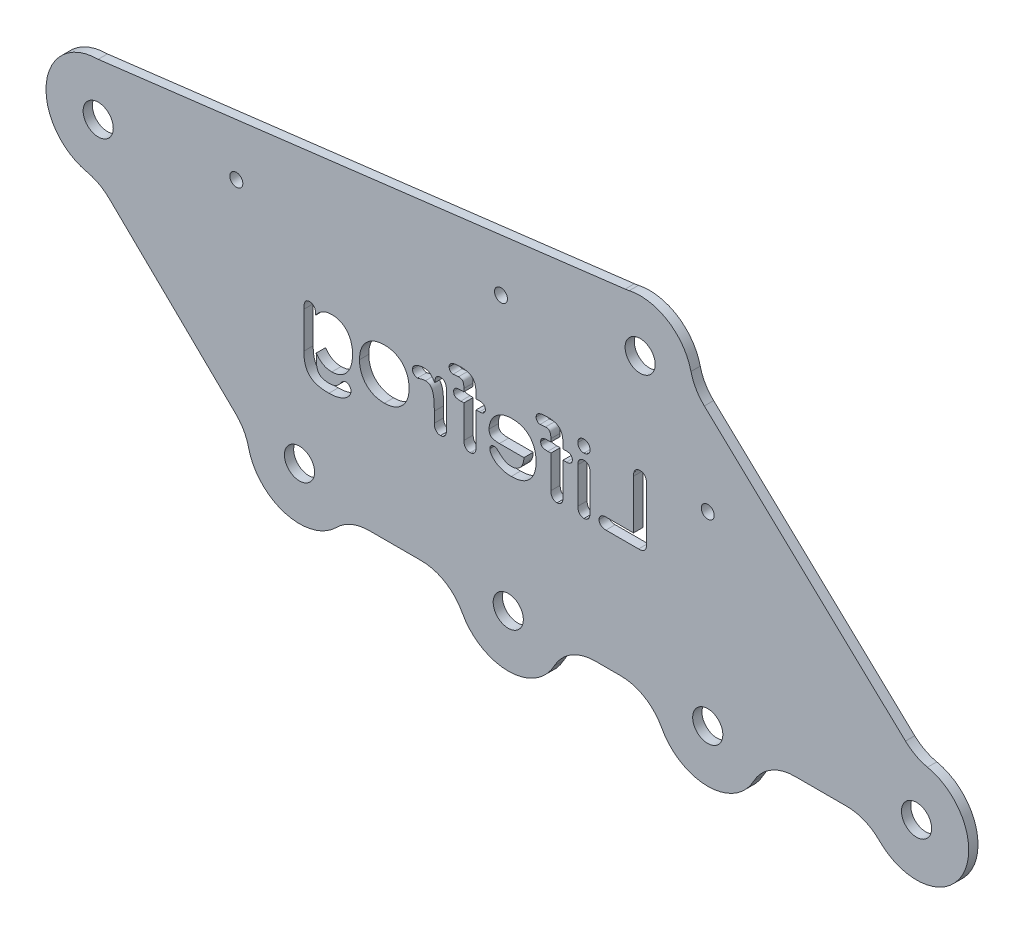
SolidWorks part; units mm, degrees
ref_plane "Front Plane" through (0, 0, 0) normal (0, 0, 1) x (1, 0, 0)
ref_plane "Top Plane" through (0, 0, 0) normal (0, 1, 0) x (1, 0, 0)
ref_plane "Right Plane" through (0, 0, 0) normal (1, 0, 0) x (0, 0, -1)
sketch "Sketch2" plane through (0, 0, 0) normal (0, 0, 1) x (1, 0, 0)
  line L0 (-96.303, -40.0195) -> (103.697, -40.0195) construction
  line L1 (56.1417, 22.4699) -> (-25.9295, 22.4699) construction
  line L2 (56.1417, 22.4699) -> (56.1417, -53.9544) construction
  line L3 (56.1417, -53.9544) -> (-159.2025, -53.9544) construction
  line L4 (-159.2025, 22.4699) -> (-159.2025, -53.9544) construction
  line L5 (-96.303, -40.0195) -> (-53.2713, -40.0195) construction
  line L6 (-96.303, -47.5195) -> (-96.303, -60.0195) construction
  line L7 (-96.303, -60.0195) -> (73.7025, -60.0195) construction
  line L8 (-96.303, -60.0195) -> (-302.9325, -60.0195) construction
  line L9 (-62.0853, -60.0195) -> (-73.2496, -62.9155) construction
  line L10 (-19.0853, -47.5195) -> (-15.8353, -47.5195) construction
  line L11 (25.9147, -47.5195) -> (25.9147, -41.2921) construction
  line L12 (-62.0853, -47.5195) -> (-107.0853, -47.5195) construction
  line L13 (-107.0853, -47.5195) -> (-107.0853, -42.5195) construction
  line L14 (-62.0853, -47.5195) -> (-58.8353, -47.5195) construction
  line L15 (-167.9726, 0) -> (-124.5853, -42.5195) construction
  line L16 (-124.5853, -42.5195) -> (-167.9726, -42.9578) construction
  line L17 (-167.9726, -42.9578) -> (-167.9726, 0) construction
  line L18 (-167.9726, -42.9578) -> (-167.9726, -60.0195) construction
  line L19 (-148.0731, -13.5847) -> (-120.8252, -40.0968)
  line L21 (-150.4726, 11.25) -> (-36.8786, 25.1494)
  line L24 (-19.8262, 11.8603) -> (23.5313, -29.0221)
  line L25 (11.3122, -40.0195) -> (103.697, -40.0195) construction
  line L26 (-41.384, 22.4699) -> (-159.2025, 22.4699) construction
  line L27 (-43.3353, -47.5195) -> (-37.8353, -47.5195)
  line L28 (-0.3353, -47.5195) -> (10.8627, -47.5195)
  line L29 (-80.8353, -47.5195) -> (-92.0333, -47.5195)
  line L30 (-50.8353, -47.5195) -> (-19.0853, -47.5195) construction
  line L31 (-7.8353, -47.5195) -> (25.9147, -47.5195) construction
  line L32 (-150.4726, 0) -> (-33.6568, 14.2936) construction
  arc A0 (-21.208, 13.1632) -> (-43.1118, 22.4699) centre (-33.6568, 14.2936) ccw construction
  circle A1 centre (-33.6568, 14.2936) radius 3.25 construction
  arc A2 (-74.5853, -47.5195) -> (-51.3689, -53.9544) centre (-62.0853, -47.5195) ccw construction
  circle A3 centre (-62.0853, -47.5195) radius 3.25 construction
  circle A4 centre (25.9147, -42.5195) radius 3.25
  circle A5 centre (-19.0853, -47.5195) radius 3.25 construction
  circle A6 centre (25.9147, -42.5195) radius 17.5 construction
  circle A7 centre (25.9147, -42.5195) radius 3.25 construction
  circle A8 centre (-107.0853, -42.5195) radius 17.5 construction
  circle A9 centre (-107.0853, -42.5195) radius 3.25 construction
  circle A10 centre (-150.4726, 0) radius 17.5 construction
  circle A11 centre (-150.4726, 0) radius 3.25 construction
  arc A12 (-150.4726, 11.25) -> (-152.8942, -10.9863) centre (-150.4726, 0) ccw
  arc A13 (-118.0513, -45.0313) -> (-99.1166, -50.4607) centre (-107.0853, -42.5195) ccw
  arc A14 (-22.7028, 16.8572) -> (-36.0054, 25.2957) centre (-33.6568, 14.2936) ccw
  arc A15 (-72.0118, -52.8136) -> (-52.1588, -52.8136) centre (-62.0853, -47.5195) ccw
  arc A16 (-29.0118, -52.8136) -> (-9.1588, -52.8136) centre (-19.0853, -47.5195) ccw
  arc A17 (17.946, -50.4607) -> (28.2849, -31.522) centre (25.9147, -42.5195) ccw
  arc A18 (-7.6288, -42.5195) -> (-9.0853, -40.0195) centre (-19.0853, -47.5195) ccw construction
  arc A19 (-31.5853, -47.5195) -> (-8.3689, -53.9544) centre (-19.0853, -47.5195) ccw construction
  circle A20 centre (-19.0853, -47.5195) radius 3.25
  circle A21 centre (-62.0853, -47.5195) radius 3.25
  circle A22 centre (-107.0853, -42.5195) radius 3.25
  circle A23 centre (-150.4726, 0) radius 3.25
  circle A24 centre (-33.6568, 14.2936) radius 3.25
  arc A25 (10.8627, -47.5195) -> (17.946, -50.4607) centre (10.8627, -57.5195) cw
  arc A26 (-148.0731, -13.5847) -> (-152.8942, -10.9863) centre (-155.0468, -20.7519) ccw
  arc A27 (-120.8252, -40.0968) -> (-118.0513, -45.0313) centre (-127.7989, -47.264) cw
  arc A28 (-92.0333, -47.5195) -> (-99.1166, -50.4607) centre (-92.0333, -57.5195) ccw
  arc A29 (-80.8353, -47.5195) -> (-72.0118, -52.8136) centre (-80.8353, -57.5195) cw
  arc A30 (-37.8353, -47.5195) -> (-29.0118, -52.8136) centre (-37.8353, -57.5195) cw
  arc A31 (-43.3353, -47.5195) -> (-52.1588, -52.8136) centre (-43.3353, -57.5195) ccw
  arc A32 (-36.0054, 25.2957) -> (-36.8786, 25.1494) centre (-38.0931, 35.0753) cw
  arc A33 (-19.8262, 11.8603) -> (-22.7028, 16.8572) centre (-12.9659, 19.136) cw
  arc A34 (23.5313, -29.0221) -> (28.2849, -31.522) centre (30.3916, -21.7464) ccw
  arc A35 (-0.3353, -47.5195) -> (-9.1588, -52.8136) centre (-0.3353, -57.5195) ccw
  point P67 (15.8369, -47.5195)
  point P70 (-150.4726, -11.25)
  point P73 (-118.3353, -42.5195)
  point P76 (-97.0075, -47.5195)
  point P79 (-73.3353, -47.5195)
  point P82 (-30.3353, -47.5195)
  point P91 (-22.4068, 14.2936)
  point P94 (25.9147, -31.2695)
  dimension "D1" = 25
  dimension "D2" = 6.5
  dimension "D5" = 35
  dimension "D6" = 6.5
  dimension "D10" = 22.5
  dimension "D11" = 22.5
  dimension "D12" = 22.5
  dimension "D13" = 6.5
  dimension "D14" = 6.5
  dimension "D15" = 22.5
  dimension "D16" = 22.5
  dimension "D17" = 22.5
  dimension "D18" = 10
  dimension "D19" = 10
  dimension "D3" = 20
  dimension "D4" = 0
  dimension "D7" = 45
  dimension "D8" = 43
  dimension "D9" = 45
extrude "Boss-Extrude1" add sketch "Sketch2" along normal blind 2
sketch "Sketch5" plane through (0, 0, 2) normal (0, 0, 1) x (1, 0, 0)
  line L1 (-106.4284, -21.9146) -> (-30.7738, -21.9146) construction
  line L2 (-106.4284, -21.9146) -> (-106.4284, -6.1743) construction
  line L3 (-106.4284, -6.1743) -> (-30.7738, -6.1743) construction
  line L4 (-30.7738, -21.9146) -> (-30.7738, -6.1743) construction
sketch "Sketch7" plane through (0, 0, 2) normal (0, 0, 1) x (1, 0, 0)
  line L0 (-150.4726, 0) -> (-33.6568, 14.2936) construction
  line L1 (-150.4726, 0) -> (-107.0853, -42.5195) construction
  line L2 (-107.0853, -42.5195) -> (25.9147, -42.5195) construction
  line L3 (25.9147, -42.5195) -> (-33.6568, 14.2936) construction
  line L5 (-107.0853, -2.5195) -> (-35.0853, -2.5195) construction
  line L6 (25.9147, -42.5195) -> (25.9147, -7.5195) construction
  line L7 (25.9147, -7.5195) -> (-64.0853, -7.5195) construction
  circle A0 centre (-120.6947, 3.6436) radius 1.4
  circle A1 centre (-63.6568, 10.6228) radius 1.4
  circle A5 centre (-19.0853, -7.5195) radius 1.4
  point P17 (0, 0)
  dimension "D1" = 2.8
  dimension "D2" = 2.8
  dimension "D4" = 30
  dimension "D5" = 2.8
  dimension "D6" = 40
  dimension "D3" = 30
  dimension "D7" = 35
  dimension "D9" = 45
extrude "Cut-Extrude4" cut sketch "Sketch7" against normal through all
sketch "Sketch8" plane through (0, 0, 0) normal (0, 0, -1) x (-1, 0, 0)
  text T0 "Lifefrog" font "Arial Rounded MT Bold" height 15
extrude "Cut-Extrude5" cut sketch "Sketch8" against normal through all
sketch "Sketch9" plane through (0, 0, 0) normal (0, 0, -1) x (-1, 0, 0)
  line L0 (59.4615, -14.7017) -> (62.4003, -14.7017) construction
  line L1 (59.4615, -12.7672) -> (62.4003, -12.7672)
  line L2 (59.4615, -16.6363) -> (62.4003, -16.6363)
  arc A0 (59.4615, -12.7672) -> (59.4615, -16.6363) centre (59.4615, -14.7017) ccw
  arc A1 (62.4003, -16.6363) -> (62.4003, -12.7672) centre (62.4003, -14.7017) ccw
  circle A2 centre (88.4097, -16.6363) radius 4.4245
  circle A3 centre (101.377, -16.6363) radius 3.8005
  point P2 (60.9309, -14.7017)
extrude "Cut-Extrude6" cut sketch "Sketch9" against normal blind 10
